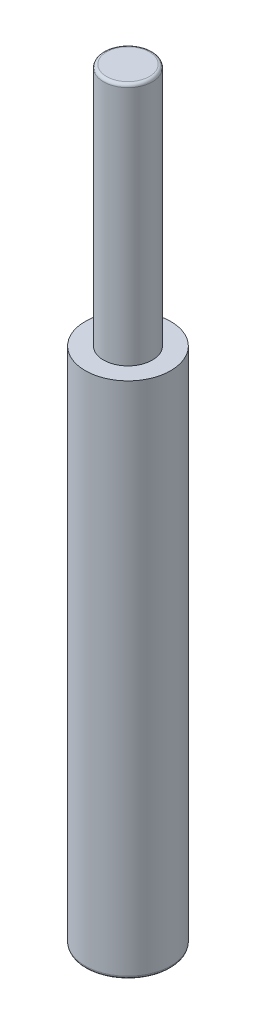
SolidWorks part; units mm, degrees
ref_plane "Front Plane" through (0, 0, 0) normal (0, 0, 1) x (1, 0, 0)
ref_plane "Top Plane" through (0, 0, 0) normal (0, 1, 0) x (1, 0, 0)
ref_plane "Right Plane" through (0, 0, 0) normal (1, 0, 0) x (0, 0, -1)
sketch "Sketch1" plane through (0, 0, 0) normal (0, 1, 0) x (1, 0, 0)
  circle A0 centre (0, 0) radius 4
  circle A1 centre (0, 0) radius 7
  dimension "D1" = 8
  dimension "D2" = 14
extrude "Boss-Extrude1" add sketch "Sketch1" along normal blind 40 contours A0 region at (0, 0, 0)
extrude "Boss-Extrude2" add sketch "Sketch1<3>" against normal blind 85 contours A1 A0 | A0 region at (0, 0, 0) region at (-6.802, 0, 0)
sketch "Sketch1<3>" plane through (0, 0, 0) normal (0, 1, 0) x (1, 0, 0) same geometry as "Sketch1"
fillet "Fillet1" radius 0.5 2 edges at (0, -85, 7) (0, 40, 4)
